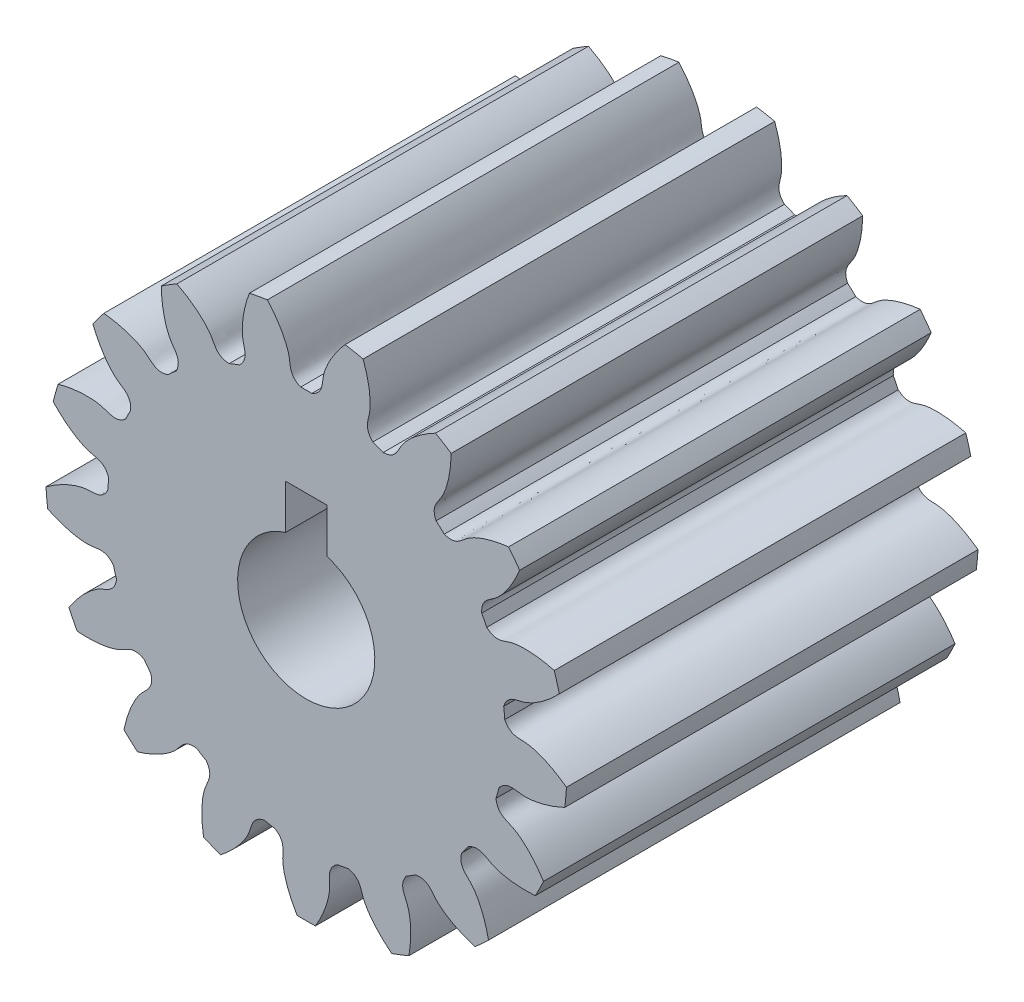
SolidWorks part; units mm, degrees
ref_plane "前视基准面" through (0, 0, 0) normal (0, 0, 1) x (1, 0, 0)
ref_plane "上视基准面" through (0, 0, 0) normal (0, 1, 0) x (1, 0, 0)
ref_plane "右视基准面" through (0, 0, 0) normal (1, 0, 0) x (0, 0, -1)
other "Configuration Table"
sketch "草图1" plane through (0, 0, 0) normal (0, 0, 1) x (1, 0, 0)
  circle A0 centre (0, 0) radius 19
extrude "凸台-拉伸1" add sketch "草图1" along normal blind 30
ref_axis "基准轴1" through (0, 0, -1.5) along (0, 0, 1)
sketch "草图2" plane through (0, 0, 0) normal (0, 0, 1) x (1, 0, 0)
  line L0 (0, 0) -> (0, 19) construction
  circle A0 centre (0, 0) radius 19 construction
  arc A1 (0.4034, 14.4944) -> (-0.4034, 14.4944) centre (0, 0) ccw
  arc A2 (6.2313, 21.4814) -> (-6.2313, 21.4814) centre (0, 0) ccw
  spline S0 degree 3 poles (0.4034, 14.4944) (1.2558, 14.8496) (1.1324, 15.5096) (1.2766, 16.1296) (1.29, 16.1823) (1.306, 16.2408) (1.3251, 16.3052) (1.3474, 16.3752) (1.3731, 16.4508) (1.4025, 16.5319) (1.4359, 16.6184) (1.4733, 16.7101) (1.5152, 16.8068) (1.5616, 16.9086) (1.6128, 17.0151) (1.669, 17.1264) (1.7304, 17.2421) (1.7972, 17.3621) (1.8696, 17.4863) (1.9478, 17.6145) (2.032, 17.7465) (2.1224, 17.8821) (2.2191, 18.0211) (2.3223, 18.1634) (2.4322, 18.3086) (2.5489, 18.4566) (2.6727, 18.6072) (2.8035, 18.7601) (2.9417, 18.9152) (3.0873, 19.0722) (3.2404, 19.2308) (3.4012, 19.3908) (3.5698, 19.552) (3.7462, 19.7141) (3.9307, 19.8769) (4.1233, 20.0401) (4.324, 20.2035) (4.533, 20.3667) (4.7503, 20.5295) (4.9761, 20.6917) (5.2103, 20.853) (5.453, 21.0131) (5.7916, 21.2269) (6.0532, 21.3811) (6.2313, 21.4814) knots 0 0 0 0 0.193883 0.199024 0.204851 0.211363 0.21856 0.226443 0.235011 0.244265 0.254205 0.264829 0.27614 0.288136 0.300817 0.314184 0.328236 0.342973 0.358397 0.374505 0.391299 0.408779 0.426944 0.445795 0.465331 0.485552 0.506459 0.528051 0.550329 0.573293 0.596941 0.621276 0.646296 0.672001 0.698392 0.725468 0.753229 0.781677 0.810809 0.840627 0.871131 0.90232 0.934195 1 1 1 1
  spline S1 degree 3 poles (-0.4034, 14.4944) (-1.2558, 14.8496) (-1.1324, 15.5096) (-1.2766, 16.1296) (-1.29, 16.1823) (-1.306, 16.2408) (-1.3251, 16.3052) (-1.3474, 16.3752) (-1.3731, 16.4508) (-1.4025, 16.5319) (-1.4359, 16.6184) (-1.4733, 16.7101) (-1.5152, 16.8068) (-1.5616, 16.9086) (-1.6128, 17.0151) (-1.669, 17.1264) (-1.7304, 17.2421) (-1.7972, 17.3621) (-1.8696, 17.4863) (-1.9478, 17.6145) (-2.032, 17.7465) (-2.1224, 17.8821) (-2.2191, 18.0211) (-2.3223, 18.1634) (-2.4322, 18.3086) (-2.5489, 18.4566) (-2.6727, 18.6072) (-2.8035, 18.7601) (-2.9417, 18.9152) (-3.0873, 19.0722) (-3.2404, 19.2308) (-3.4012, 19.3908) (-3.5698, 19.552) (-3.7462, 19.7141) (-3.9307, 19.8769) (-4.1233, 20.0401) (-4.324, 20.2035) (-4.533, 20.3667) (-4.7503, 20.5295) (-4.9761, 20.6917) (-5.2103, 20.853) (-5.453, 21.0131) (-5.7916, 21.2269) (-6.0532, 21.3811) (-6.2313, 21.4814) knots 0 0 0 0 0.193883 0.199024 0.204851 0.211363 0.21856 0.226443 0.235011 0.244265 0.254205 0.264829 0.27614 0.288136 0.300817 0.314184 0.328236 0.342973 0.358397 0.374505 0.391299 0.408779 0.426944 0.445795 0.465331 0.485552 0.506459 0.528051 0.550329 0.573293 0.596941 0.621276 0.646296 0.672001 0.698392 0.725468 0.753229 0.781677 0.810809 0.840627 0.871131 0.90232 0.934195 1 1 1 1
extrude "切除-拉伸1" cut sketch "草图2" along normal through all
pattern_circular "阵列(圆周)1" count 17 every 21.176 about axis through (0, 0, -1.5) along (0, 0, 1) of "切除-拉伸1"
sketch "草图3" plane through (0, 0, 0) normal (0, 0, 1) x (1, 0, 0)
  circle A0 centre (0, 0) radius 17 construction
  dimension "Dn" = 34
sketch "草图4" plane through (0, 0, 30) normal (0, 0, 1) x (1, 0, 0)
  line L0 (0, 0) -> (-1.5, 0)
  line L1 (-1.5, 0) -> (-1.5, 8)
  line L2 (-1.5, 8) -> (1.5, 8)
  line L3 (1.5, 8) -> (1.5, 0)
  line L4 (1.5, 0) -> (0, 0)
  circle A0 centre (0, 0) radius 5
extrude "切除-拉伸2" cut sketch "草图4" against normal through all contours L1 A0 L3 L4 L0 | L3 A0 L1 L0 L4 | A0 L3 L2 L1 region at (0, -0.5704, 30) region at (0, 2.4625, 30) region at (0, 6.4612, 30)
